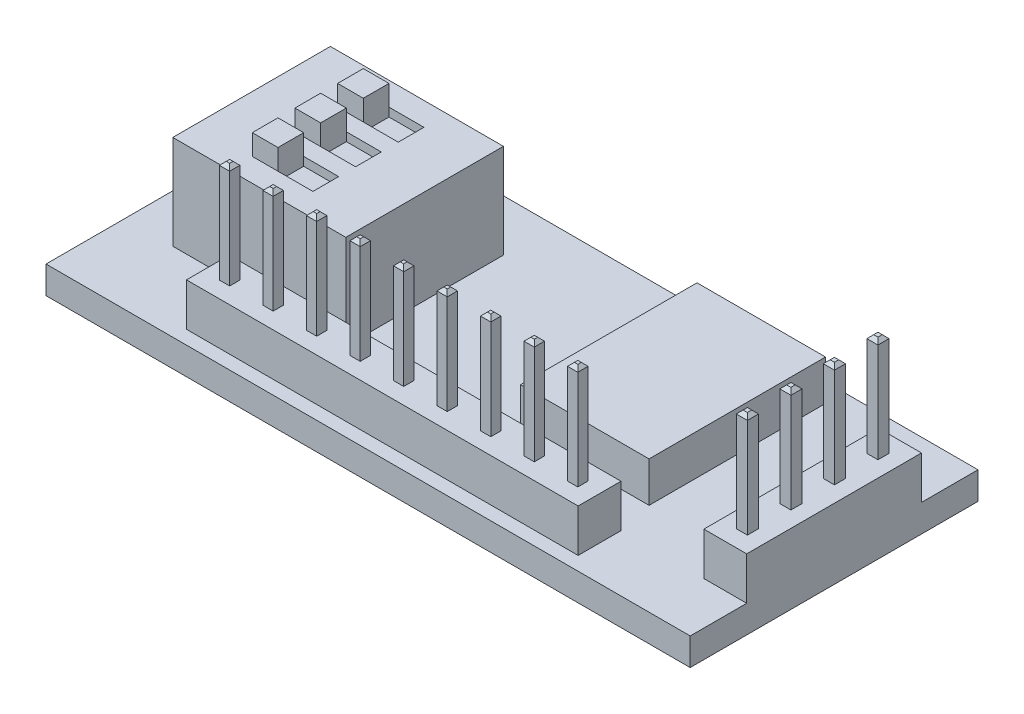
SolidWorks part; units mm, degrees
material "ABS"
ref_plane "Front Plane" through (0, 0, 0) normal (0, 0, 1) x (1, 0, 0)
ref_plane "Top Plane" through (0, 0, 0) normal (0, 1, 0) x (1, 0, 0)
ref_plane "Right Plane" through (0, 0, 0) normal (1, 0, 0) x (0, 0, -1)
sketch "Sketch1" plane through (0, 0, 0) normal (0, 1, 0) x (1, 0, 0)
  line L0 (0, 8.4) -> (0, 0) construction
  line L1 (-18.8, 8.4) -> (18.8, 8.4)
  line L2 (-18.8, 8.4) -> (-18.8, -8.4)
  line L3 (-18.8, -8.4) -> (18.8, -8.4)
  line L4 (18.8, 8.4) -> (18.8, -8.4)
  line L5 (0, 0) -> (0, -8.4) construction
  dimension "D1" = 16.8
  dimension "D2" = 37.6
extrude "Boss-Extrude1" add sketch "Sketch1" along normal blind 1.6
sketch "Sketch3" plane through (0, 1.6, 0) normal (0, 1, 0) x (1, 0, 0)
  line L0 (18.8, 8.4) -> (-18.8, 8.4) construction
  line L1 (-11.4, -5.1) -> (11.46, -5.1)
  line L2 (-11.4, -5.1) -> (-11.4, -7.6)
  line L3 (-11.4, -7.6) -> (11.46, -7.6)
  line L4 (11.46, -5.1) -> (11.46, -7.6)
  line L5 (18.8, -8.4) -> (18.8, 8.4) construction
  point P4 (11.46, -6.35)
  dimension "D1" = 2.5
  dimension "D2" = 22.86
  dimension "D3" = 16
  dimension "D4" = 30.2
extrude "Boss-Extrude3" add sketch "Sketch3" along normal blind 2.5
sketch "Sketch2" plane through (0, 1.6, 0) normal (0, 1, 0) x (1, 0, 0)
  line L0 (-7.89, -6.65) -> (-7.29, -6.65)
  line L1 (-10.43, -6.65) -> (-9.83, -6.65)
  line L2 (-10.43, -6.65) -> (-10.43, -6.05)
  line L3 (-10.43, -6.05) -> (-9.83, -6.05)
  line L4 (-9.83, -6.65) -> (-9.83, -6.05)
  line L5 (-7.89, -6.65) -> (-7.89, -6.05)
  line L6 (-7.89, -6.05) -> (-7.29, -6.05)
  line L7 (-7.29, -6.65) -> (-7.29, -6.05)
  line L8 (-5.35, -6.65) -> (-4.75, -6.65)
  line L9 (-5.35, -6.65) -> (-5.35, -6.05)
  line L10 (-5.35, -6.05) -> (-4.75, -6.05)
  line L11 (-4.75, -6.65) -> (-4.75, -6.05)
  line L12 (-2.81, -6.65) -> (-2.21, -6.65)
  line L13 (-2.81, -6.65) -> (-2.81, -6.05)
  line L14 (-2.81, -6.05) -> (-2.21, -6.05)
  line L15 (-2.21, -6.65) -> (-2.21, -6.05)
  line L16 (-0.27, -6.65) -> (0.33, -6.65)
  line L17 (-0.27, -6.65) -> (-0.27, -6.05)
  line L18 (-0.27, -6.05) -> (0.33, -6.05)
  line L19 (0.33, -6.65) -> (0.33, -6.05)
  line L20 (2.27, -6.65) -> (2.87, -6.65)
  line L21 (2.27, -6.65) -> (2.27, -6.05)
  line L22 (2.27, -6.05) -> (2.87, -6.05)
  line L23 (2.87, -6.65) -> (2.87, -6.05)
  line L24 (4.81, -6.65) -> (5.41, -6.65)
  line L25 (4.81, -6.65) -> (4.81, -6.05)
  line L26 (4.81, -6.05) -> (5.41, -6.05)
  line L27 (5.41, -6.65) -> (5.41, -6.05)
  line L28 (7.35, -6.65) -> (7.95, -6.65)
  line L29 (7.35, -6.65) -> (7.35, -6.05)
  line L30 (7.35, -6.05) -> (7.95, -6.05)
  line L31 (7.95, -6.65) -> (7.95, -6.05)
  line L32 (9.89, -6.65) -> (10.49, -6.65)
  line L33 (9.89, -6.65) -> (9.89, -6.05)
  line L34 (9.89, -6.05) -> (10.49, -6.05)
  line L35 (10.49, -6.65) -> (10.49, -6.05)
  line L38 (-11.4, -6.35) -> (-10.43, -6.35) construction
  line L39 (-11.4, -5.1) -> (-11.4, -7.6) construction
  line L40 (10.49, -6.35) -> (11.46, -6.35) construction
  line L41 (11.46, -7.6) -> (11.46, -5.1) construction
  dimension "D1" = 0.6
  dimension "D3" = 2.54
  dimension "D2" = 9
extrude "Boss-Extrude2" add sketch "Sketch2" along normal blind 8.5
sketch "Sketch4" plane through (0, 1.6, 0) normal (0, 1, 0) x (1, 0, 0)
  line L0 (-18.8, 8.4) -> (-18.8, -8.4) construction
  line L1 (16.3, 5.1) -> (18.8, 5.1)
  line L2 (16.3, 5.1) -> (16.3, -5.1)
  line L3 (16.3, -5.1) -> (18.8, -5.1)
  line L4 (18.8, 5.1) -> (18.8, -5.1)
  line L5 (-18.8, 5.1) -> (-10.4, 5.1) construction
  line L6 (-18.8, 5.1) -> (-18.8, -5.1) construction
  line L7 (-18.8, -5.1) -> (-10.4, -5.1) construction
  line L8 (-10.4, 5.1) -> (-10.4, -5.1) construction
  line L9 (-10.4, 0) -> (0, 0) construction
  line L10 (18.8, -8.4) -> (18.8, 8.4) construction
  dimension "D1" = 2.5
  dimension "D2" = 10.2
  dimension "D3" = 8.4
extrude "Boss-Extrude4" add sketch "Sketch4" along normal blind 2.5 separate body
sketch "Sketch5" plane through (18.8, 0, 0) normal (1, 0, 0) x (0, 0, -1)
  line L0 (-3.51, 2.55) -> (-1.57, 2.55) construction
  line L1 (-4.11, 3.15) -> (-3.51, 3.15)
  line L2 (-4.11, 3.15) -> (-4.11, 2.55)
  line L3 (-4.11, 2.55) -> (-3.51, 2.55)
  line L4 (-3.51, 3.15) -> (-3.51, 2.55)
  line L5 (-1.57, 3.15) -> (-0.97, 3.15)
  line L6 (-1.57, 3.15) -> (-1.57, 2.55)
  line L7 (-1.57, 2.55) -> (-0.97, 2.55)
  line L8 (-0.97, 3.15) -> (-0.97, 2.55)
  line L9 (0.97, 3.15) -> (1.57, 3.15)
  line L10 (0.97, 3.15) -> (0.97, 2.55)
  line L11 (0.97, 2.55) -> (1.57, 2.55)
  line L12 (1.57, 3.15) -> (1.57, 2.55)
  line L13 (3.51, 3.15) -> (4.11, 3.15)
  line L14 (3.51, 3.15) -> (3.51, 2.55)
  line L15 (3.51, 2.55) -> (4.11, 2.55)
  line L16 (4.11, 3.15) -> (4.11, 2.55)
  line L17 (-0.97, 2.55) -> (0.97, 2.55) construction
  line L18 (1.57, 2.55) -> (3.51, 2.55) construction
  line L19 (4.11, 2.85) -> (5.1, 2.85) construction
  line L20 (5.1, 4.1) -> (5.1, 1.6) construction
  line L21 (-4.11, 2.85) -> (-5.1, 2.85) construction
  line L22 (-5.1, 4.1) -> (-5.1, 1.6) construction
  dimension "D1" = 2.54
  dimension "D2" = 0.6
extrude "Boss-Extrude5" [suppressed] add sketch "Sketch5" along normal blind 6
chamfer "Chamfer2" [suppressed] distance 0.2 angle 45
sketch "Sketch6" plane through (0, 1.6, 0) normal (0, 1, 0) x (1, 0, 0)
  line L0 (16.3, 5.1) -> (16.3, -5.1) construction
  line L1 (-3.2, 7.4) -> (4.8, 7.4)
  line L2 (-3.2, 7.4) -> (-3.2, -3.1)
  line L3 (-3.2, -3.1) -> (4.8, -3.1)
  line L4 (4.8, 7.4) -> (4.8, -3.1)
  line L5 (18.8, 8.4) -> (-18.8, 8.4) construction
  dimension "D1" = 8
  dimension "D2" = 10.5
  dimension "D3" = 11.5
  dimension "D4" = 1
extrude "Boss-Extrude6" [suppressed] add sketch "Sketch6" along normal blind 2.5
sketch "Sketch7" [suppressed] plane through (0, 1.6, 0) normal (0, 1, 0) x (1, 0, 0)
  line L0 (18.8, 8.4) -> (-18.8, 8.4) construction
  line L1 (-3.9, 6.9) -> (3.6, 6.9)
  line L2 (-3.9, 6.9) -> (-3.9, -0.9)
  line L3 (-3.9, -0.9) -> (3.6, -0.9)
  line L4 (3.6, 6.9) -> (3.6, -0.9)
  line L5 (-10.4, -5.1) -> (-10.4, 5.1) construction
  point P6 (-0.15, 6.9)
  dimension "D1" = 7.8
  dimension "D2" = 7.5
  dimension "D3" = 1.5
  dimension "D4" = 6.5
extrude "Boss-Extrude7" [suppressed] add sketch "Sketch7" along normal blind 2.5
sketch "Sketch8" [suppressed] plane through (0, 4.1, 0) normal (0, 1, 0) x (1, 0, 0)
  line L0 (-3.85, 0.16) -> (-3.25, 0.16)
  line L1 (-6.39, 0.16) -> (-5.79, 0.16)
  line L2 (-6.39, 0.16) -> (-6.39, -0.44)
  line L3 (-6.39, -0.44) -> (-5.79, -0.44)
  line L4 (-5.79, 0.16) -> (-5.79, -0.44)
  line L5 (-3.85, 0.16) -> (-3.85, -0.44)
  line L6 (-3.85, -0.44) -> (-3.25, -0.44)
  line L7 (-3.25, 0.16) -> (-3.25, -0.44)
  line L8 (-1.31, 0.16) -> (-0.71, 0.16)
  line L9 (-1.31, 0.16) -> (-1.31, -0.44)
  line L10 (-1.31, -0.44) -> (-0.71, -0.44)
  line L11 (-0.71, 0.16) -> (-0.71, -0.44)
  line L12 (-3.85, 2.7) -> (-3.25, 2.7)
  line L13 (-3.85, 2.7) -> (-3.85, 2.1)
  line L14 (-3.85, 2.1) -> (-3.25, 2.1)
  line L15 (-3.25, 2.7) -> (-3.25, 2.1)
  line L16 (-1.31, 2.7) -> (-0.71, 2.7)
  line L17 (-1.31, 2.7) -> (-1.31, 2.1)
  line L18 (-1.31, 2.1) -> (-0.71, 2.1)
  line L19 (-0.71, 2.7) -> (-0.71, 2.1)
  line L20 (-3.85, 5.24) -> (-3.25, 5.24)
  line L21 (-3.85, 5.24) -> (-3.85, 4.64)
  line L22 (-3.85, 4.64) -> (-3.25, 4.64)
  line L23 (-3.25, 5.24) -> (-3.25, 4.64)
  line L24 (-1.31, 5.24) -> (-0.71, 5.24)
  line L25 (-1.31, 5.24) -> (-1.31, 4.64)
  line L26 (-1.31, 4.64) -> (-0.71, 4.64)
  line L27 (-0.71, 5.24) -> (-0.71, 4.64)
  line L28 (-6.39, 2.7) -> (-5.79, 2.7)
  line L29 (-6.39, 2.7) -> (-6.39, 2.1)
  line L30 (-6.39, 2.1) -> (-5.79, 2.1)
  line L31 (-5.79, 2.7) -> (-5.79, 2.1)
  line L32 (-6.39, 5.24) -> (-5.79, 5.24)
  line L33 (-6.39, 5.24) -> (-6.39, 4.64)
  line L34 (-6.39, 4.64) -> (-5.79, 4.64)
  line L35 (-5.79, 5.24) -> (-5.79, 4.64)
  line L36 (-3.55, 5.24) -> (-3.55, 6.9) construction
  line L37 (-3.2, 6.9) -> (-3.9, 6.9) construction
  line L38 (-0.71, 2.4) -> (-1.6, 2.4) construction
  line L39 (-1.6, -1.5) -> (-1.6, 6.3) construction
  line L40 (-3.55, -0.44) -> (-3.55, -0.9) construction
  line L41 (-3.9, -0.9) -> (-3.2, -0.9) construction
  dimension "D3" = 2.54
  dimension "D4" = 2.54
  dimension "D5" = 0.6
  dimension "D1" = 3
  dimension "D2" = 3
extrude "Boss-Extrude8" [suppressed] add sketch "Sketch8" along normal blind 6
chamfer "Chamfer3" [suppressed] distance 0.2 angle 45
sketch "Sketch9" plane through (0, 1.6, 0) normal (0, 1, 0) x (1, 0, 0)
  line L0 (18.8, 8.4) -> (-18.8, 8.4) construction
  line L1 (3.5, 7.3) -> (11, 7.3)
  line L2 (3.5, 7.3) -> (3.5, -3)
  line L3 (3.5, -3) -> (11, -3)
  line L4 (11, 7.3) -> (11, -3)
  line L5 (18.8, -8.4) -> (18.8, 8.4) construction
  dimension "D1" = 10.3
  dimension "D2" = 7.5
  dimension "D3" = 11.4
  dimension "D4" = 15.3
extrude "Boss-Extrude9" add sketch "Sketch9" along normal blind 2.35
sketch "Sketch10" plane through (0, 4.1, 0) normal (0, 1, 0) x (1, 0, 0)
  line L0 (17.225, -0.945) -> (17.875, -0.945)
  line L1 (17.225, -0.945) -> (17.225, -1.595)
  line L2 (17.225, -1.595) -> (17.875, -1.595)
  line L3 (17.875, -0.945) -> (17.875, -1.595)
  line L4 (17.225, 1.595) -> (17.875, 1.595)
  line L5 (17.225, 1.595) -> (17.225, 0.945)
  line L6 (17.225, 0.945) -> (17.875, 0.945)
  line L7 (17.875, 1.595) -> (17.875, 0.945)
  line L8 (17.225, 4.135) -> (17.875, 4.135)
  line L9 (17.225, 4.135) -> (17.225, 3.485)
  line L10 (17.225, 3.485) -> (17.875, 3.485)
  line L11 (17.875, 4.135) -> (17.875, 3.485)
  line L12 (17.55, 5.1) -> (17.55, 4.135) construction
  line L13 (17.225, -3.485) -> (17.875, -3.485)
  line L14 (17.225, -3.485) -> (17.225, -4.135)
  line L15 (17.225, -4.135) -> (17.875, -4.135)
  line L16 (17.875, -3.485) -> (17.875, -4.135)
  line L17 (18.8, 5.1) -> (16.3, 5.1) construction
  line L18 (17.55, -4.135) -> (17.55, -5.1) construction
  line L19 (16.3, -5.1) -> (18.8, -5.1) construction
  dimension "D1" = 0.65
  dimension "D3" = 2.54
  dimension "D2" = 4
extrude "Boss-Extrude10" add sketch "Sketch10" along normal up to surface (6 mm away) up to face at (10.19, 10.1, 6.35)
chamfer "Chamfer1" distance 0.2 angle 45 52 edges at (10.19, 10.1, 6.05) (10.49, 10.1, 6.35) (10.19, 10.1, 6.65) (9.89, 10.1, 6.35) (7.65, 10.1, 6.05) (7.95, 10.1, 6.35) (7.65, 10.1, 6.65) (7.35, 10.1, 6.35) (5.11, 10.1, 6.05) (5.41, 10.1, 6.35) (5.11, 10.1, 6.65) (4.81, 10.1, 6.35) (2.57, 10.1, 6.05) (2.87, 10.1, 6.35) (2.57, 10.1, 6.65) (2.27, 10.1, 6.35) (0.03, 10.1, 6.05) (0.33, 10.1, 6.35) (0.03, 10.1, 6.65) (-0.27, 10.1, 6.35) (-2.51, 10.1, 6.05) (-2.21, 10.1, 6.35) (-2.51, 10.1, 6.65) (-2.81, 10.1, 6.35) (-5.05, 10.1, 6.05) (-4.75, 10.1, 6.35) (-5.05, 10.1, 6.65) (-5.35, 10.1, 6.35) (-7.59, 10.1, 6.05) (-7.29, 10.1, 6.35) (-7.59, 10.1, 6.65) (-7.89, 10.1, 6.35) (-10.13, 10.1, 6.05) (-9.83, 10.1, 6.35) (-10.13, 10.1, 6.65) (-10.43, 10.1, 6.35) (17.225, 10.1, 3.81) (17.55, 10.1, 3.485) (17.875, 10.1, 3.81) (17.55, 10.1, 4.135) (17.225, 10.1, 1.27) (17.55, 10.1, 0.945) (17.875, 10.1, 1.27) (17.55, 10.1, 1.595) (17.225, 10.1, -1.27) (17.55, 10.1, -1.595) (17.875, 10.1, -1.27) (17.55, 10.1, -0.945) (17.225, 10.1, -3.81) (17.55, 10.1, -4.135) (17.875, 10.1, -3.81) (17.55, 10.1, -3.485)
sketch "Sketch11" plane through (0, 1.6, 0) normal (0, 1, 0) x (1, 0, 0)
  line L0 (-18.8, 8.4) -> (-18.8, -8.4) construction
  line L1 (-16, 5.4) -> (-5.9, 5.4)
  line L2 (-16, 5.4) -> (-16, -3.8)
  line L3 (-16, -3.8) -> (-5.9, -3.8)
  line L4 (-5.9, 5.4) -> (-5.9, -3.8)
  line L5 (18.8, 8.4) -> (-18.8, 8.4) construction
  dimension "D1" = 10.1
  dimension "D2" = 9.2
  dimension "D3" = 12.9
  dimension "D4" = 12.2
extrude "Boss-Extrude11" add sketch "Sketch11" along normal blind 5.5
sketch "Sketch12" plane through (0, 7.1, 0) normal (0, 1, 0) x (1, 0, 0)
  line L0 (-12.72, 2.54) -> (-12.72, 1.55) construction
  line L1 (-12.72, 4.04) -> (-9.18, 4.04)
  line L2 (-12.72, 4.04) -> (-12.72, 2.54)
  line L3 (-12.72, 2.54) -> (-9.18, 2.54)
  line L4 (-9.18, 4.04) -> (-9.18, 2.54)
  line L5 (-12.72, 1.55) -> (-9.18, 1.55)
  line L6 (-12.72, 1.55) -> (-12.72, 0.05)
  line L7 (-12.72, 0.05) -> (-9.18, 0.05)
  line L8 (-9.18, 1.55) -> (-9.18, 0.05)
  line L9 (-12.72, -0.94) -> (-9.18, -0.94)
  line L10 (-12.72, -0.94) -> (-12.72, -2.44)
  line L11 (-12.72, -2.44) -> (-9.18, -2.44)
  line L12 (-9.18, -0.94) -> (-9.18, -2.44)
  line L13 (-12.72, 0.05) -> (-12.72, -0.94) construction
  line L14 (-10.95, 4.04) -> (-10.95, 5.4) construction
  line L15 (-5.9, 5.4) -> (-16, 5.4) construction
  line L16 (-10.95, -2.44) -> (-10.95, -3.8) construction
  line L17 (-16, -3.8) -> (-5.9, -3.8) construction
  dimension "D1" = 6.48
  dimension "D2" = 3.54
  dimension "D3" = 1.5
extrude "Cut-Extrude1" cut sketch "Sketch12" against normal blind 0.5
sketch "Sketch13" plane through (0, 6.6, 0) normal (0, 1, 0) x (1, 0, 0)
  line L0 (-12.72, 2.54) -> (-9.18, 2.54) construction
  line L1 (-12.72, 4.04) -> (-11.22, 4.04)
  line L2 (-12.72, 4.04) -> (-12.72, 2.54)
  line L3 (-12.72, 2.54) -> (-11.22, 2.54)
  line L4 (-11.22, 4.04) -> (-11.22, 2.54)
  line L5 (-12.72, 0.05) -> (-9.18, 0.05) construction
  line L6 (-12.72, 1.55) -> (-11.22, 1.55)
  line L7 (-12.72, 1.55) -> (-12.72, 0.05)
  line L8 (-12.72, 0.05) -> (-11.22, 0.05)
  line L9 (-11.22, 1.55) -> (-11.22, 0.05)
  line L10 (-12.72, -2.44) -> (-9.18, -2.44) construction
  line L11 (-12.72, -0.94) -> (-11.22, -0.94)
  line L12 (-12.72, -0.94) -> (-12.72, -2.44)
  line L13 (-12.72, -2.44) -> (-11.22, -2.44)
  line L14 (-11.22, -0.94) -> (-11.22, -2.44)
extrude "Boss-Extrude12" add sketch "Sketch13" along normal blind 1.7 separate body
ref_plane "Plane1" through (0, 0, 6.35) normal (0, 0, -1) x (-1, 0, 0)
ref_plane "Plane2" through (10.19, 0, 0) normal (1, 0, 0) x (0, 0, -1)
ref_plane "Plane3" through (-10.13, 0, 0) normal (-1, 0, 0) x (0, 0, 1)
ref_axis "Axis1" through (10.19, 3.81, 6.35) along (0, 1, 0)
ref_axis "Axis2" through (-10.13, 3.81, 6.35) along (0, 1, 0)
